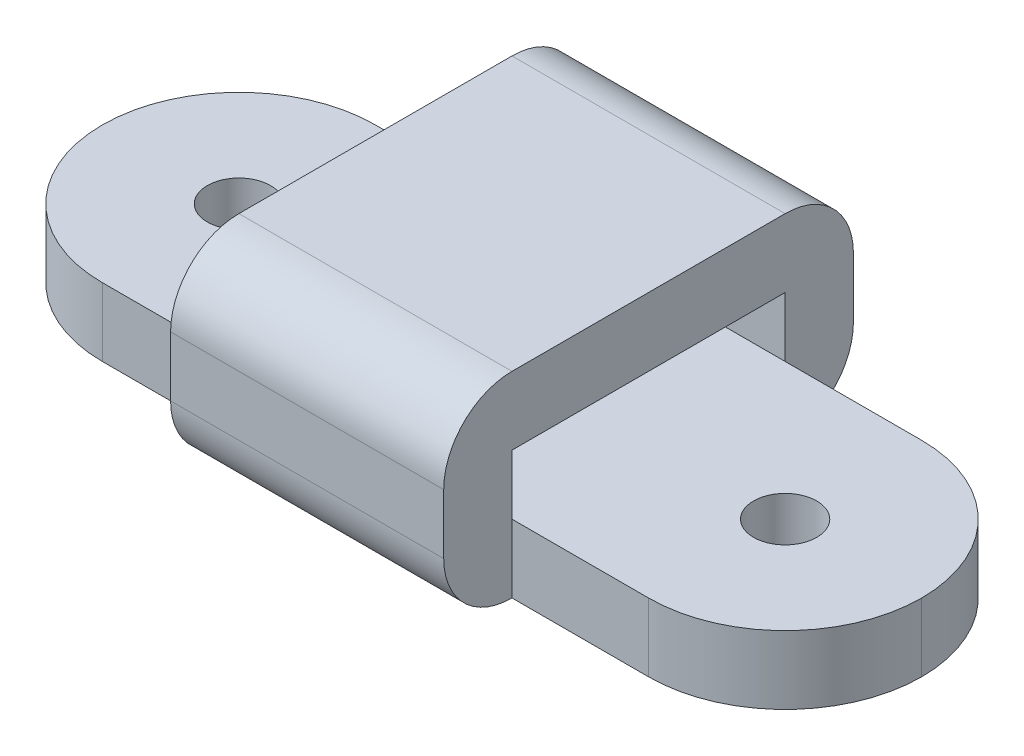
SolidWorks part; units mm, degrees
ref_plane "Front Plane" through (0, 0, 0) normal (0, 0, 1) x (1, 0, 0)
ref_plane "Top Plane" through (0, 0, 0) normal (0, 1, 0) x (1, 0, 0)
ref_plane "Right Plane" through (0, 0, 0) normal (1, 0, 0) x (0, 0, -1)
sketch "Sketch1" plane through (0, 0, 0) normal (0, 1, 0) x (1, 0, 0)
  line L0 (-24, 0) -> (24, 0) construction
  line L1 (-24, -8) -> (24, -8)
  line L2 (-24, -8) -> (-24, 8)
  line L3 (-24, 8) -> (24, 8)
  line L4 (24, -8) -> (24, 8)
  line L5 (-24, -8) -> (24, 8) construction
  line L6 (-24, 8) -> (24, -8) construction
  line L7 (0, -8) -> (0, 8) construction
  circle A0 centre (-16, 0) radius 1.85
  circle A1 centre (16, 0) radius 1.85
  point P0 (0, 0)
  dimension "D4" = 3.7
  dimension "D1" = 48
  dimension "D2" = 16
  dimension "D3" = 16
extrude "Boss-Extrude1" add sketch "Sketch1" along normal blind 4
ref_plane "Plane1" through (-8, 0, 0) normal (-1, 0, 0) x (0, 0, 1)
sketch "Sketch2" plane through (-8, 0, 0) normal (-1, 0, 0) x (0, 0, 1)
  line L0 (-8, 4) -> (-8, 0) construction
  line L1 (-8, 4) -> (-8, 0)
  line L2 (0, -1000) -> (0, 49000) construction
  line L3 (-8, 0) -> (-12, 0)
  line L4 (-12, 0) -> (-12, 11.5)
  line L5 (-12, 11.5) -> (12, 11.5)
  line L6 (0, 11.5) -> (0, 7.5) construction
  line L7 (8, 7.5) -> (-8, 7.5)
  line L8 (-8, 7.5) -> (-8, 4)
  line L9 (8, 7.5) -> (8, 4)
  line L10 (12, 0) -> (12, 11.5)
  line L11 (8, 0) -> (12, 0)
  line L12 (8, 4) -> (8, 0)
  dimension "D1" = 3.5
extrude "Boss-Extrude2" add sketch "Sketch2" against normal blind 16 contours L4 L5 L10 L11 L12 L9 L7 L8 L1 L3
fillet "Fillet1" radius 4 4 edges at (0, 11.5, 12) (0, 0, 12) (0, 0, -12) (0, 11.5, -12)
fillet "Fillet2" radius 8 4 edges at (-24, 2, 8) (-24, 2, -8) (24, 2, 8) (24, 2, -8)
